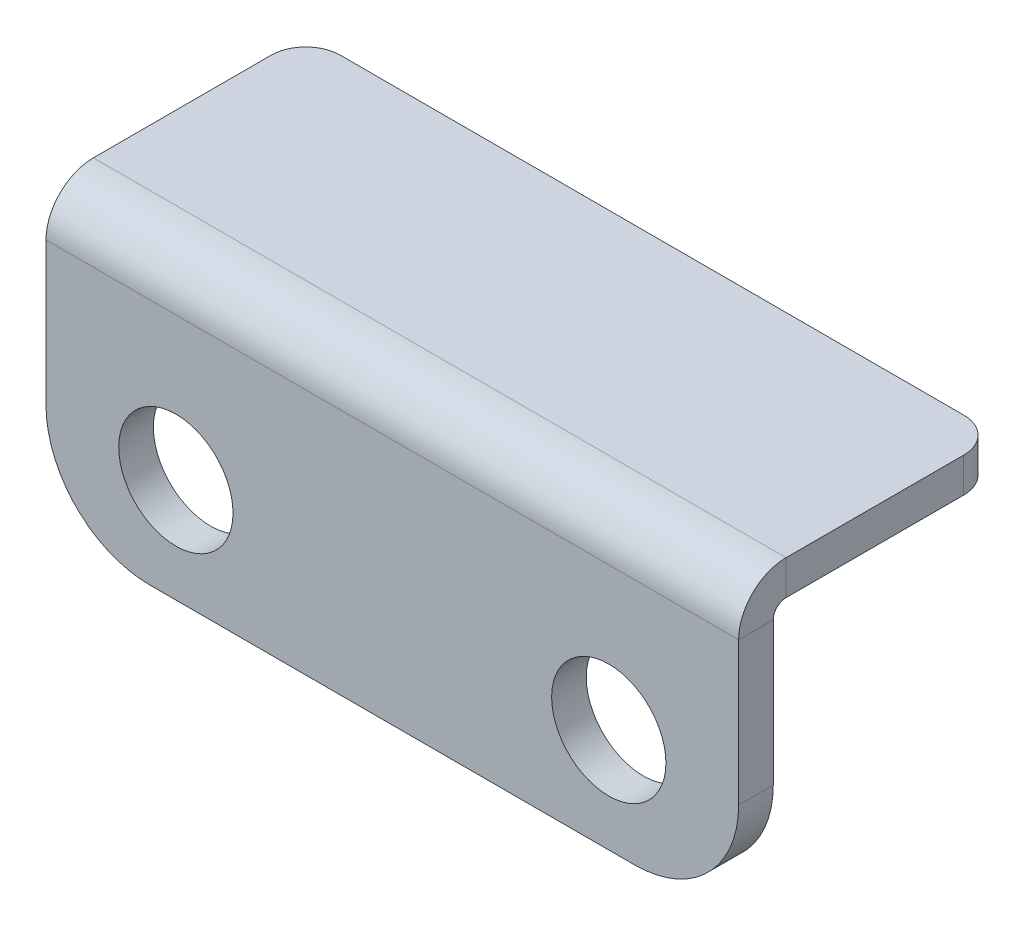
SolidWorks part; units mm, degrees
note: The reader was unsure of these and kept them because the rebuilt part matched: flange length of "边线-法兰1".
ref_plane "前视基准面" through (0, 0, 0) normal (0, 0, 1) x (1, 0, 0)
ref_plane "上视基准面" through (0, 0, 0) normal (0, 1, 0) x (1, 0, 0)
ref_plane "右视基准面" through (0, 0, 0) normal (1, 0, 0) x (0, 0, -1)
sketch "草图2" plane through (0, 0, 0) normal (0, 0, 1) x (1, 0, 0)
  line L1 (-20, 8.5) -> (20, 8.5)
  line L2 (-20, 8.5) -> (-20, -8.5)
  line L3 (-20, -8.5) -> (20, -8.5)
  line L4 (20, 8.5) -> (20, -8.5)
  line L5 (-20, 8.5) -> (20, -8.5) construction
  line L6 (-20, -8.5) -> (20, 8.5) construction
  point P0 (0, 0)
  dimension "D1" = 17
  dimension "D2" = 40
base flange "基体-法兰1" sketch "草图2" thickness 2 reverse thickness direction no parameters "D1"=0.7366
edge flange "边线-法兰1" sketch "草图9" flange angle 90 flange length 15 flange position material inside bend radius 0.7366 thickness 2 relief rectangular parameters "D6"=10
sketch "草图9" plane through (0, 8.5, -2) normal (0, 1, 0) x (1, 0, 0)
  line L0 (20, 0) -> (-20, 0) construction
  line L1 (20, 0) -> (-20, 0)
  line L2 (-20, 0) -> (-20, 13)
  line L3 (-20, 13) -> (20, 13)
  line L4 (20, 13) -> (20, 0)
bend "边线折弯1" bend radius 0.7366 bend angle 90 parameters "D5"=1
sketch "草图10" plane through (0, 0, -2) normal (0, 0, -1) x (-1, 0, 0)
  line L0 (0, -2.5) -> (0, -8.5) construction
  line L1 (-12.5, -2.5) -> (12.5, -2.5) construction
  line L2 (20, -8.5) -> (-20, -8.5) construction
  circle A0 centre (-12.5, -2.5) radius 3.3
  circle A1 centre (12.5, -2.5) radius 3.3
  point P3 (0, -2.5)
  dimension "D1" = 25
  dimension "D2" = 6.6
  dimension "D3" = 6.6
  dimension "D4" = 6
extrude "切除-拉伸1" cut sketch "草图10" against normal blind 10 normal cut yes
fillet "圆角1" radius 6 2 edges at (-20, -8.5, -1) (20, -8.5, -1)
fillet "圆角2" radius 2 2 edges at (-20, 7.5, -15) (20, 7.5, -15)
sketch "折弯-线1" plane through (0, 0, 0) normal (0, 1, 0) x (1, 0, 0)
sketch "边界框1" plane through (0, 0, 0) normal (0, 1, 0) x (1, 0, 0)
sheet metal parameters "钣金6" thickness 2 parameters "D1"=0.7366
flat pattern "平板型式6" [suppressed]
sketch "折弯-线2" plane through (0, 0, 0) normal (0, 1, 0) x (1, 0, 0)
sketch "边界框2" [suppressed] plane through (0, 0, 0) normal (0, 1, 0) x (1, 0, 0)
sheet metal parameters "钣金7" thickness 2 parameters "D1"=0.7366
flat pattern "平板型式6" [suppressed]
sketch "折弯-线2" plane through (0, 0, 0) normal (0, 1, 0) x (1, 0, 0)
sketch "边界框2" [suppressed] plane through (0, 0, 0) normal (0, 1, 0) x (1, 0, 0)
bend of the flat pattern "展开-<边线折弯1>1"
sheet metal parameters "钣金8" thickness 2 parameters "D1"=0.7366
flat pattern "平板型式6"
sketch "折弯-线2" plane through (0, 0, 0) normal (0, 0, 1) x (1, 0, 0)
  line L0 (20, 7.1273) -> (-20, 7.1273) construction
  line L1 (20, 7.1273) -> (-20, 7.1273) construction
sketch3d "边界框2" [suppressed]
  line L0 (-20, 20.7546, 0) -> (20, 20.7546, 0) construction
  line L1 (-20, -8.5, 0) -> (20, -8.5, 0) construction
  line L2 (-20, 20.7546, 0) -> (-20, -8.5, 0) construction
  line L3 (20, 20.7546, 0) -> (20, -8.5, 0) construction
bend of the flat pattern "展开-<边线折弯1>1"
